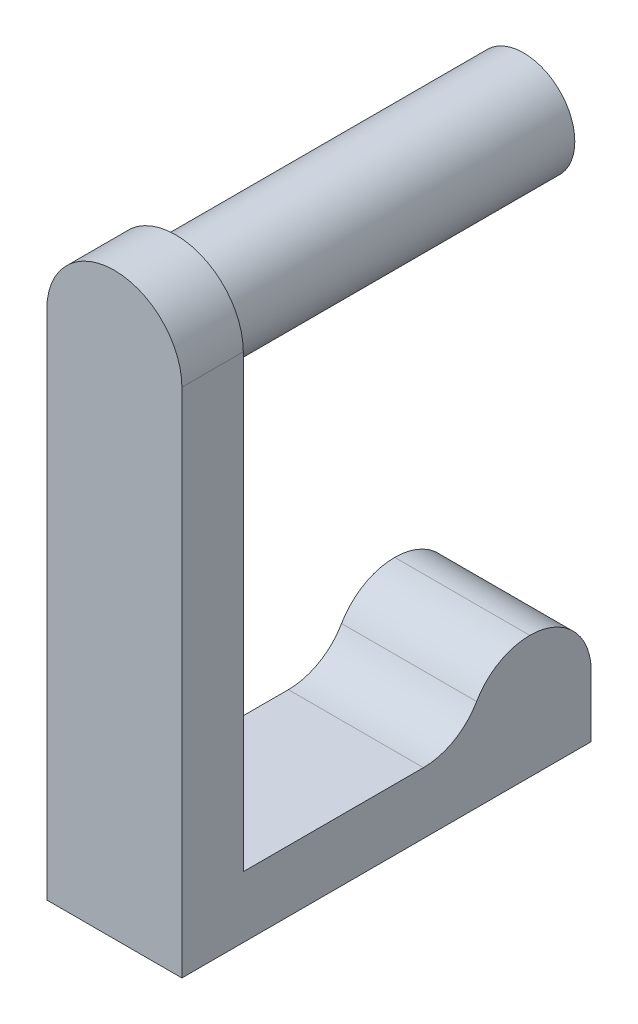
SolidWorks part; units mm, degrees
ref_plane "Płaszczyzna przednia" through (0, 0, 0) normal (0, 0, 1) x (1, 0, 0)
ref_plane "Płaszczyzna górna" through (0, 0, 0) normal (0, 1, 0) x (1, 0, 0)
ref_plane "Płaszczyzna prawa" through (0, 0, 0) normal (1, 0, 0) x (0, 0, -1)
sketch "Sketch1" plane through (0, 0, 0) normal (0, 0, 1) x (1, 0, 0)
  circle A0 centre (-6.2414, 9.3437) radius 2.5
  dimension "D1" = 5
extrude "Boss-Extrude1" add sketch "Sketch1" against normal blind 17
sketch "Sketch2" plane through (0, 0, 0) normal (0, 0, 1) x (1, 0, 0)
  line L1 (-9.5414, 9.3437) -> (-2.9414, 9.3437)
  line L2 (-9.5414, 9.3437) -> (-9.5414, -15.6563)
  line L3 (-9.5414, -15.6563) -> (-2.9414, -15.6563)
  line L4 (-2.9414, 9.3437) -> (-2.9414, -15.6563)
  circle A0 centre (-6.2414, 9.3437) radius 2.5
  circle A1 centre (-6.2414, 9.3437) radius 2.5 construction
  circle A2 centre (-6.2414, 9.3437) radius 3.3
  circle M7 centre (-6.2414, 9.3437) radius 2.5
  dimension "D2" = 25
  dimension "D1" = 0.8
extrude "Boss-Extrude2" add sketch "Sketch2" along normal blind 3 separate body contours L1 A2 M7 | A2 L2 L3 L4 | L1 A2 M7 | A0 region at (-6.2414, 11.9175, 0) region at (-3.3414, 9.2699, 0) region at (-6.2414, -4.4401, 0)
sketch "Sketch3" plane through (0, 0, 0) normal (0, 0, -1) x (-1, 0, 0)
  line L0 (9.5414, 9.3437) -> (9.5414, -15.6563) construction
  line L1 (2.9414, -12.6563) -> (9.5414, -12.6563)
  line L2 (2.9414, -12.6563) -> (2.9414, -15.6563)
  line L3 (2.9414, -15.6563) -> (9.5414, -15.6563)
  line L4 (9.5414, -12.6563) -> (9.5414, -15.6563)
  dimension "D1" = 3
extrude "Boss-Extrude3" add sketch "Sketch3" along normal blind 17
sketch "Sketch4" plane through (0, -12.6563, 0) normal (0, 1, 0) x (1, 0, 0)
  line L0 (-9.5414, 17) -> (-9.5414, 0) construction
  line L1 (-9.5414, 17) -> (-2.9414, 17)
  line L2 (-9.5414, 17) -> (-9.5414, 11)
  line L3 (-9.5414, 11) -> (-2.9414, 11)
  line L4 (-2.9414, 17) -> (-2.9414, 11)
  line L5 (-2.9414, 17) -> (-2.9414, 0) construction
  dimension "D1" = 6
extrude "Boss-Extrude4" add sketch "Sketch4" along normal blind 3
fillet "Fillet1" radius 3 1 edges at (-6.2414, -9.6563, -11)
fillet "Fillet2" radius 3 1 edges at (-6.2414, -12.6563, -11)
fillet "Fillet3" radius 3 1 edges at (-6.2414, -9.6563, -17)
